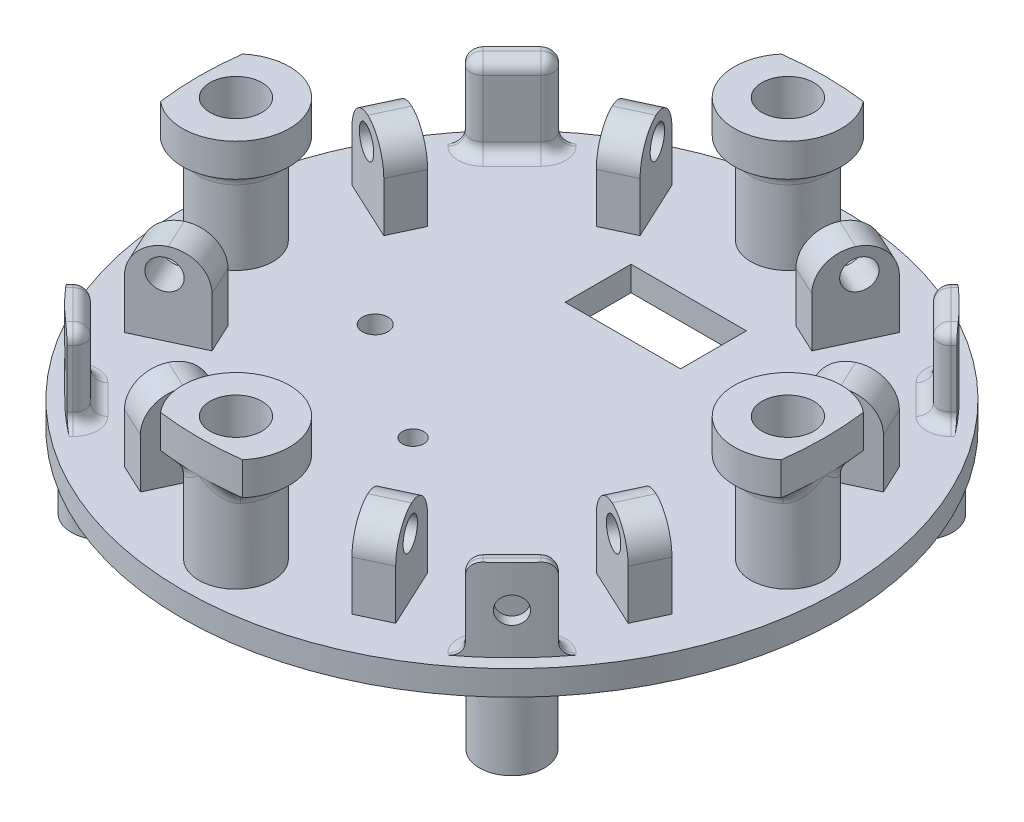
SolidWorks part; units mm, degrees
ref_plane "Alzado" through (0, 0, 0) normal (0, 0, 1) x (1, 0, 0)
ref_plane "Planta" through (0, 0, 0) normal (0, 1, 0) x (1, 0, 0)
ref_plane "Vista lateral" through (0, 0, 0) normal (1, 0, 0) x (0, 0, -1)
sketch "Sketch1" plane through (0, 60, 0) normal (0, 1, 0) x (1, 0, 0)
  circle A0 centre (0, 0) radius 40
  dimension "D1" = 80
extrude "Boss-Extrude1" add sketch "Sketch1" along normal blind 3
sketch "Sketch2" plane through (0, 63, 0) normal (0, 1, 0) x (1, 0, 0)
  line L0 (0, 0) -> (-16.9047, -36.2523) construction
  line L4 (-32.2577, -12.8353) -> (-30.5672, -16.4605)
  line L5 (-32.2577, -12.8353) -> (-25.0072, -9.4543)
  line L6 (-25.0072, -9.4543) -> (-23.3168, -13.0795)
  line L7 (-23.3168, -13.0795) -> (-30.5672, -16.4605)
  line L8 (0, 0) -> (0, -14.7934) construction
  line L9 (0, 0) -> (-13.6253, 0) construction
  line L10 (0, 0) -> (-27.1469, -27.1469) construction
  line L11 (-9.4543, -25.0072) -> (-13.0795, -23.3168)
  line L12 (-13.0795, -23.3168) -> (-16.4605, -30.5672)
  line L13 (-12.8353, -32.2577) -> (-16.4605, -30.5672)
  line L14 (-12.8353, -32.2577) -> (-9.4543, -25.0072)
  circle A1 centre (0, 0) radius 40 construction
  dimension "D1" = 4
  dimension "D2" = 20
  dimension "D3" = 2
  dimension "D4" = 8
  dimension "D5" = 45
extrude "Boss-Extrude2" add sketch "Sketch2" along normal blind 10
sketch "Sketch3" plane through (0.8452, 0, 1.8126) normal (0.4226, 0, 0.9063) x (0.9063, 0, -0.4226)
  line L0 (-34.6598, 73) -> (-26.6598, 73) construction
  circle A0 centre (-31, 70) radius 1.8
  point P4 (-31, 70)
  dimension "D1" = 3.6
  dimension "D2" = 3
extrude "Cut-Extrude1" cut sketch "Sketch3" against normal blind 9
sketch "Sketch4" plane through (-1.8126, 0, -0.8452) normal (-0.9063, 0, -0.4226) x (-0.4226, 0, 0.9063)
  line L0 (26.6598, 73) -> (34.6598, 73) construction
  circle A0 centre (31, 70) radius 1.8
  point P4 (31, 70)
  dimension "D1" = 3.6
  dimension "D2" = 3
extrude "Cut-Extrude2" cut sketch "Sketch4" against normal blind 9
ref_axis "Axis1" through (0, 63, 0) along (0, -1, 0)
pattern_circular "CirPattern1" count 4 over 360 about axis through (0, 63, 0) along (0, -1, 0) of "Boss-Extrude2", "Cut-Extrude1", "Cut-Extrude2"
fillet "Fillet1" radius 4 16 edges at (-11.2669, 73, 24.162) (-14.6479, 73, 31.4125) (-24.162, 73, 11.2669) (-31.4125, 73, 14.6479) (-31.4125, 73, -14.6479) (-24.162, 73, -11.2669) (-11.2669, 73, -24.162) (-14.6479, 73, -31.4125) (11.2669, 73, -24.162) (14.6479, 73, -31.4125) (24.162, 73, -11.2669) (31.4125, 73, -14.6479) (24.162, 73, 11.2669) (31.4125, 73, 14.6479) (11.2669, 73, 24.162) (14.6479, 73, 31.4125)
sketch "Sketch5" plane through (0, 63, 0) normal (0, 1, 0) x (1, 0, 0)
  circle A0 centre (0, 0) radius 2.1093 construction
sketch "Sketch7" plane through (0, 63, 0) normal (0, 1, 0) x (1, 0, 0)
sketch "Sketch9" plane through (0, 63, 0) normal (0, 1, 0) x (1, 0, 0)
  circle A0 centre (0, -33.4949) radius 4.5
  circle A5 centre (-33.4949, 0) radius 4.5
  circle A7 centre (0, 33.4949) radius 4.5
  circle A9 centre (33.4949, 0) radius 4.5
  point P12 (0, 0)
  point P17 (0, 0)
  dimension "D1" = 9
  dimension "D3" = 4
extrude "Boss-Extrude3" add sketch "Sketch9" along normal up to surface (15 mm away)
sketch "Sketch10" plane through (0, 78, 0) normal (0, 1, 0) x (1, 0, 0)
  circle A0 centre (0, -33.4949) radius 3.15
  circle A1 centre (-33.4949, 0) radius 3.15
  circle A2 centre (0, 33.4949) radius 3.15
  circle A3 centre (33.4949, 0) radius 3.15
  point P12 (0, 0)
  dimension "D1" = 6.3
  dimension "D2" = 4
extrude "Cut-Extrude3" cut sketch "Sketch10" against normal blind 10
sketch "Sketch11" plane through (-31.4125, 0, 14.6479) normal (-0.9063, 0, 0.4226) x (0.4226, 0, 0.9063)
  line L0 (2, 69) -> (-2, 69) construction
  point P0 (0, 69)
sketch "Sketch12" plane through (0, 63, 0) normal (0, 1, 0) x (1, 0, 0)
  line L0 (0, 0) -> (-40, 0) construction
  circle A0 centre (0, 0) radius 40 construction
sketch "Sketch13" plane through (0, 60, 0) normal (0, -1, 0) x (1, 0, 0)
  line L1 (0, 0) -> (11.1766, 0) construction
  line L2 (0, 0) -> (40, 0) construction
  line L3 (-13.759, -9.1) -> (18.0386, -9.1) construction
  line L4 (0, 0) -> (-19.6628, 0) construction
  line L6 (0, 0) -> (0, -27.9284) construction
  line L7 (-13.759, 9.1) -> (18.0386, 9.1) construction
  circle A2 centre (0, -9.1) radius 3.0819 construction
  circle A3 centre (0, 9.1) radius 3.0819 construction
  dimension "D1" = 9.1
sketch "Sketch14" plane through (0, 63, 0) normal (0, 1, 0) x (1, 0, 0)
  line L0 (0, 0) -> (14.9462, 0) construction
  line L1 (0, 0) -> (0, 14.5968) construction
  line L2 (0, 0) -> (-13.5539, 0) construction
  line L3 (0, 0) -> (-28.2843, -28.2843) construction
  circle A0 centre (-24.7487, -24.7487) radius 1.55
  circle A2 centre (-24.7487, 24.7487) radius 1.55
  circle A3 centre (24.7487, 24.7487) radius 1.55
  circle A4 centre (24.7487, -24.7487) radius 1.55
  point P17 (0, 0)
  dimension "D2" = 3.1
  dimension "D1" = 45
  dimension "D3" = 5
  dimension "D4" = 4
sketch "Croquis3" plane through (0, 63, 0) normal (0, 1, 0) x (1, 0, 0)
  line L0 (-29.826, -24.1692) -> (-28.4118, -22.755)
  line L1 (-24.1692, -29.826) -> (-22.755, -28.4118)
  line L2 (0, 0) -> (-28.2843, -28.2843) construction
  line L3 (-28.4118, -22.755) -> (-22.755, -28.4118)
  line L4 (-24.1692, 29.826) -> (-22.755, 28.4118)
  line L5 (-29.826, 24.1692) -> (-28.4118, 22.755)
  line L6 (-22.755, 28.4118) -> (-28.4118, 22.755)
  line L7 (29.826, 24.1692) -> (28.4118, 22.755)
  line L8 (24.1692, 29.826) -> (22.755, 28.4118)
  line L9 (28.4118, 22.755) -> (22.755, 28.4118)
  line L10 (24.1692, -29.826) -> (22.755, -28.4118)
  line L11 (29.826, -24.1692) -> (28.4118, -22.755)
  line L12 (22.755, -28.4118) -> (28.4118, -22.755)
  arc A0 (-29.826, -24.1692) -> (-24.1692, -29.826) centre (0, 0) ccw
  arc A1 (-24.1692, 29.826) -> (-29.826, 24.1692) centre (0, 0) ccw
  arc A2 (29.826, 24.1692) -> (24.1692, 29.826) centre (0, 0) ccw
  arc A3 (24.1692, -29.826) -> (29.826, -24.1692) centre (0, 0) ccw
  point P23 (0, 0)
  dimension "D1" = 2
  dimension "D2" = 2
  dimension "D4" = 8
  dimension "D5" = 4
  dimension "D3" = 4
extrude "Saliente-Extruir1" add sketch "Croquis3" along normal blind 10
sketch "Sketch16" plane through (25.5834, 0, -25.5834) normal (-0.7071, 0, 0.7071) x (0.7071, 0, 0.7071)
  circle A0 centre (0, 68) radius 1.6
  dimension "D1" = 3.2
extrude "Cut-Extrude4" cut sketch "Sketch16" against normal blind 2 from offset 0.8 offset against normal yes
pattern_circular "CirPattern2" count 4 over 360 about axis through (0, 63, 0) along (0, 1, 0) of "Cut-Extrude4"
sketch "Sketch17" plane through (0, 60, 0) normal (0, -1, 0) x (1, 0, 0)
  line L0 (0, 0) -> (0, 32.8251) construction
  circle A0 centre (0, 32.8251) radius 3.5
  circle A1 centre (0, 0) radius 40
  circle A2 centre (0, 0) radius 40
  dimension "D2" = 7
  dimension "D1" = 0
sketch "Sketch19" plane through (0, 60, 0) normal (0, -1, 0) x (1, 0, 0)
  circle A0 centre (-24.7487, 24.7487) radius 3.95
  circle A1 centre (24.7487, 24.7487) radius 3.95
  circle A2 centre (24.7487, -24.7487) radius 3.95
  circle A3 centre (-24.7487, -24.7487) radius 3.95
  point P12 (0, 0)
  dimension "D1" = 7.9
extrude "Boss-Extrude4" add sketch "Sketch19" along normal blind 9
sketch "Sketch20" plane through (0, 51, 0) normal (0, -1, 0) x (1, 0, 0)
  circle A0 centre (-24.7487, 24.7487) radius 2.1
  circle A1 centre (24.7487, 24.7487) radius 2.1
  circle A2 centre (24.7487, -24.7487) radius 2.1
  circle A3 centre (-24.7487, -24.7487) radius 2.1
  point P12 (0, 0)
  dimension "D1" = 4.2
extrude "Cut-Extrude5" cut sketch "Sketch20" against normal blind 8
fillet "Fillet5" radius 1.5 32 edges at (-29.1189, 63, 23.4621) (-23.4621, 63, 29.1189) (23.4621, 63, 29.1189) (29.1189, 63, 23.4621) (29.1189, 63, -23.4621) (23.4621, 63, -29.1189) (-23.4621, 63, -29.1189) (-29.1189, 63, -23.4621) (-23.4621, 73, -29.1189) (-29.1189, 73, -23.4621) (-29.1189, 73, 23.4621) (-23.4621, 73, 29.1189) (23.4621, 73, 29.1189) (29.1189, 73, 23.4621) (23.4621, 73, -29.1189) (29.1189, 73, -23.4621) (25.5834, 63, -25.5834) (-25.5834, 63, -25.5834) (-25.5834, 63, 25.5834) (25.5834, 63, 25.5834) (28.4118, 68, -22.755) (25.5834, 73, -25.5834) (22.755, 68, -28.4118) (-22.755, 68, -28.4118) (-25.5834, 73, -25.5834) (-28.4118, 68, -22.755) (-28.4118, 68, 22.755) (-22.755, 68, 28.4118) (-25.5834, 73, 25.5834) (28.4118, 68, 22.755) (22.755, 68, 28.4118) (25.5834, 73, 25.5834)
sketch "Sketch21" plane through (0, 63, 0) normal (0, 1, 0) x (1, 0, 0)
  line L0 (0, 21.3479) -> (0, 27.028) construction
  line L1 (-7, 21.4575) -> (7, 21.4575)
  line L2 (-7, 21.4575) -> (-7, 13.4575)
  line L3 (-7, 13.4575) -> (7, 13.4575)
  line L4 (7, 21.4575) -> (7, 13.4575)
  line L5 (-7, 21.4575) -> (7, 13.4575) construction
  line L6 (-7, 13.4575) -> (7, 21.4575) construction
  point P0 (0, 17.4575)
  dimension "D1" = 14
  dimension "D2" = 8
extrude "Cut-Extrude6" cut sketch "Sketch21" against normal blind 6
ref_plane "Plane2" through (0, 63, 0) normal (0, 1, 0) x (1, 0, 0)
sketch "Sketch22" plane through (0, 63, 0) normal (0, 1, 0) x (1, 0, 0)
  circle A0 centre (-16.2, -0.397) radius 1.55
  circle A1 centre (-2, -10) radius 1.3
extrude "Cut-Extrude7" cut sketch "Sketch22" against normal blind 10
sketch "Sketch23" plane through (0, 78, 0) normal (0, 1, 0) x (1, 0, 0)
  circle A0 centre (-33.4949, 0) radius 3.15
  arc A2 (-37.6665, -4.9848) -> (-37.6665, 4.9848) centre (-33.4949, 0) ccw
  arc A3 (-37.6665, 4.9848) -> (-37.6665, -4.9848) centre (0, 0) ccw
  circle A4 centre (0, 33.4949) radius 3.15
  arc A5 (-4.9848, 37.6665) -> (4.9848, 37.6665) centre (0, 33.4949) ccw
  arc A6 (4.9848, 37.6665) -> (-4.9848, 37.6665) centre (0, 0) ccw
  circle A7 centre (33.4949, 0) radius 3.15
  arc A8 (37.6665, 4.9848) -> (37.6665, -4.9848) centre (33.4949, 0) ccw
  arc A9 (37.6665, -4.9848) -> (37.6665, 4.9848) centre (0, 0) ccw
  circle A10 centre (0, -33.4949) radius 3.15
  arc A11 (4.9848, -37.6665) -> (-4.9848, -37.6665) centre (0, -33.4949) ccw
  arc A12 (-4.9848, -37.6665) -> (4.9848, -37.6665) centre (0, 0) ccw
  point P22 (0, 0)
  dimension "D1" = 13
  dimension "D2" = 4
extrude "Boss-Extrude5" add sketch "Sketch23" against normal blind 4
fillet "Fillet4" radius 2 4 edges at (0, 74, -28.9949) (33.4949, 74, 4.5) (0, 74, 37.9949) (-33.4949, 74, 4.5)
